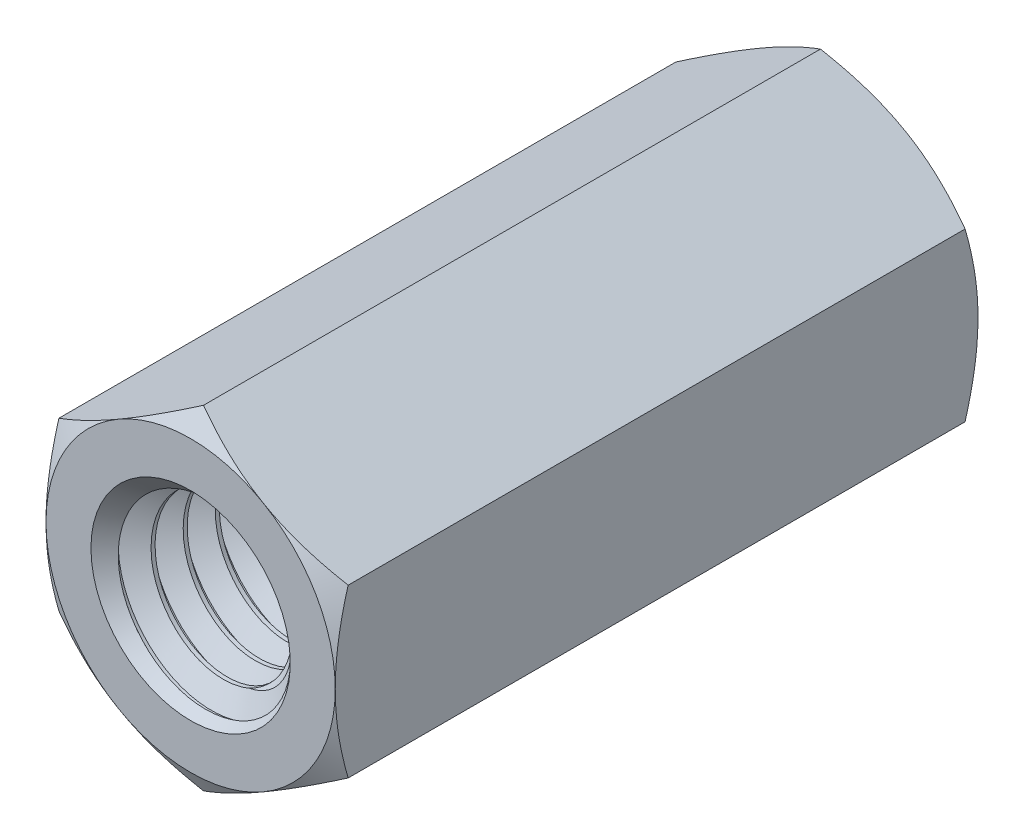
SolidWorks part; units mm, degrees
ref_plane "Front Plane" through (0, 0, 0) normal (0, 0, 1) x (1, 0, 0)
ref_plane "Top Plane" through (0, 0, 0) normal (0, 1, 0) x (1, 0, 0)
ref_plane "Right Plane" through (0, 0, 0) normal (1, 0, 0) x (0, 0, -1)
sketch "Sketch3" plane through (0, 0, 0) normal (1, 0, 0) x (0, 0, -1)
  line L0 (-5, 0) -> (5, 0) construction
  line L1 (0, 2.25) -> (0, -2.25) construction
  line L2 (-5, 1.5) -> (-5, -1.5) construction
  point P2 (0.2, 0)
  point P3 (-0.2, 0)
  dimension "Length" = 10
  dimension "Min Thread Length" = 4.8
  dimension "D1" = 4.8
  dimension "Thread Dia" = 3
  dimension "Hex" = 4.5
sketch "Sketch1" plane through (0, 0, 0) normal (0, 0, 1) x (1, 0, 0)
  line L1 (0, 2.5981) -> (-2.25, 1.299)
  line L2 (-2.25, 1.299) -> (-2.25, -1.299)
  line L3 (-2.25, -1.299) -> (0, -2.5981)
  line L4 (0, -2.5981) -> (2.25, -1.299)
  line L5 (2.25, -1.299) -> (2.25, 1.299)
  line L6 (2.25, 1.299) -> (0, 2.5981)
  circle A0 centre (0, 0) radius 2.25 construction
  circle A1 centre (0, 0) radius 1.5
extrude "Extrude1" add sketch "Sketch1" along normal up to vertex (5 mm away) and the other way up to vertex (5 mm away) up to point (0, 0, 5) other way up to point (0, 0, -5)
sketch "Sketch11" plane through (0, 0, -5) normal (0, 0, -1) x (-1, 0, 0)
  circle A0 centre (0, 0) radius 1.5 construction
  circle A1 centre (0, 0) radius 1.5
curve "Helix/Spiral1" pitch 0.5 height 10.5 radius 1.5 centre (0, 0, -5) axis (0, 0, 1) start towards (0, 1, 0) parameters "Pitch"=0.5
sketch "Sketch12" plane through (0, 0, 0) normal (1, 0, 0) x (0, 0, -1)
  line L0 (5.4375, 1.5) -> (5, 1.5)
  line L1 (5.4375, 1.5) -> (5.25, 1.1752)
  line L2 (5.25, 1.1752) -> (5.1875, 1.1752)
  line L3 (5.1875, 1.1752) -> (5, 1.5)
  line L4 (5.2187, 1.1752) -> (5.2187, 1.5) construction
  line L5 (5.3438, 1.3376) -> (5.0938, 1.3376) construction
  dimension "D1" = 0.0625
  dimension "D2" = 0.25
  dimension "D3" = 60
sweep "Sweep1" add profiles "Sketch12" path "Helix/Spiral1"
sketch "Sketch6" plane through (0, 0, -5) normal (0, 0, -1) x (-1, 0, 0)
  line L6 (0, 2.5981) -> (-2.25, 1.299)
  line L7 (-2.25, 1.299) -> (-2.25, -1.299)
  line L8 (-2.25, -1.299) -> (0, -2.5981)
  line L9 (0, -2.5981) -> (2.25, -1.299)
  line L10 (2.25, -1.299) -> (2.25, 1.299)
  line L11 (2.25, 1.299) -> (0, 2.5981)
  line L12 (0, 2.5981) -> (-2.25, 1.299)
  line L13 (-2.25, 1.299) -> (-2.25, -1.299)
  line L14 (-2.25, -1.299) -> (0, -2.5981)
  line L15 (0, -2.5981) -> (2.25, -1.299)
  line L16 (2.25, -1.299) -> (2.25, 1.299)
  line L17 (2.25, 1.299) -> (0, 2.5981)
  dimension "D1" = 0
extrude "Extrude2" cut sketch "Sketch6" along normal through all
sketch "Sketch7" plane through (0, 0, -5) normal (0, 0, -1) x (-1, 0, 0)
  circle A2 centre (0, 0) radius 1.5508
  circle A3 centre (0, 0) radius 1.5508
  dimension "D1" = 0.0508
extrude "Extrude3" cut sketch "Sketch7" against normal through all draft 43
sketch "Sketch8" plane through (0, 0, -5) normal (0, 0, -1) x (-1, 0, 0)
  circle A0 centre (0, 0) radius 2.25 construction
  circle A1 centre (0, 0) radius 2.25
extrude "Extrude4" cut sketch "Sketch8" against normal through all draft 60 flip side to cut
mirror "Mirror1" about plane through (0, 0, 0) normal (0, 0, 1) of "Extrude2", "Extrude3", "Extrude4"
sketch "Sketch9" [suppressed] plane through (0, 0, 0) normal (1, 0, 0) x (0, 0, -1)
  line L1 (-1.2, 1.1353) -> (1.2, 1.1353)
  line L2 (-1.2, 1.1353) -> (-1.2, 0)
  line L3 (-1.2, 0) -> (1.2, 0)
  line L4 (1.2, 1.1353) -> (1.2, 0)
  line L7 (-6, 0) -> (6, 0) construction
revolve "Revolve" [suppressed] add sketch "Sketch9" angle 360 about L0
sketch "Sketch10" [suppressed] plane through (0, 0, 0) normal (1, 0, 0) x (0, 0, -1)
  line L0 (6, 1.25) -> (1.2, 1.25)
  line L1 (-6, 1.25) -> (-1.2, 1.25)
  line L2 (1.2, 1.25) -> (1.2, -1.25)
  line L3 (-6, -1.25) -> (-1.2, -1.25)
  line L4 (-1.2, 1.25) -> (-1.2, -1.25)
  line L5 (1.2, -1.25) -> (6, -1.25)
equation "\"D1@Sketch3\" = \"Min Thread Length@Sketch3\""
equation "\"D3@Helix/Spiral1\" = \"Length@Sketch3\"+\"Pitch@Helix/Spiral1\""
equation "\"D1@Sketch12\" = \"Pitch@Helix/Spiral1\"*.125"
equation "\"D2@Sketch12\" = \"Pitch@Helix/Spiral1\"*.5"
